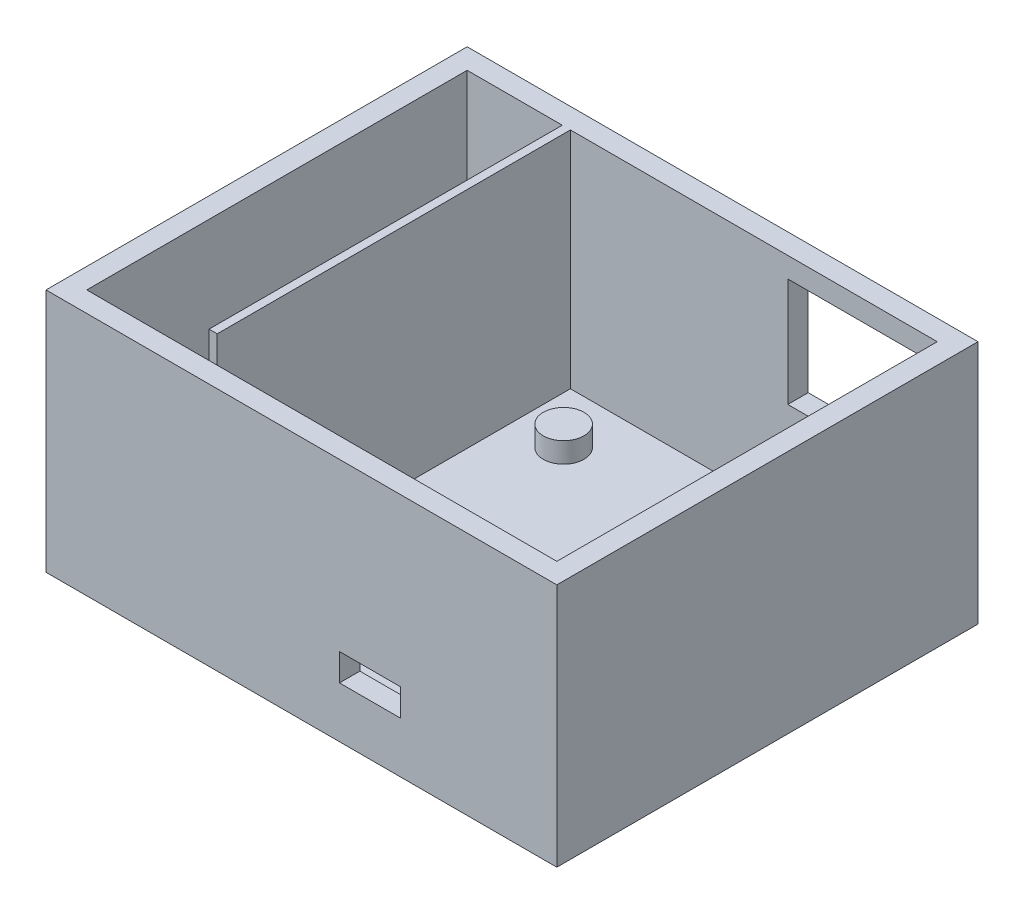
SolidWorks part; units mm, degrees
ref_plane "Front Plane" through (0, 0, 0) normal (0, 0, 1) x (1, 0, 0)
ref_plane "Top Plane" through (0, 0, 0) normal (0, 1, 0) x (1, 0, 0)
ref_plane "Right Plane" through (0, 0, 0) normal (1, 0, 0) x (0, 0, -1)
sketch "Sketch1" plane through (0, 0, 0) normal (0, 1, 0) x (1, 0, 0)
  line L0 (-55.2, 0) -> (-54, 0)
  line L1 (0, 0) -> (-54, 0)
  line L2 (0, 0) -> (0, -56)
  line L3 (0, -56) -> (-54, -56)
  line L4 (-54, 0) -> (-54, -56)
  line L5 (3, 3) -> (-72.2, 3)
  line L6 (3, 3) -> (3, -59)
  line L7 (3, -59) -> (-72.2, -59)
  line L8 (-72.2, 3) -> (-72.2, -59)
  line L9 (-69.2, 0) -> (-55.2, 0)
  line L10 (-69.2, 0) -> (-69.2, -56)
  line L11 (-69.2, -56) -> (-55.2, -56)
  line L12 (-55.2, 0) -> (-55.2, -56)
  line L13 (-55.2, -56) -> (-54, -56)
  circle A0 centre (-47, -8) radius 3
  circle A1 centre (-5, -8) radius 3
  circle A2 centre (-5, -50) radius 3
  circle A3 centre (-47, -50) radius 3
  point P21 (0, 0)
  point P22 (0, 0)
  point P23 (0, 0)
  point P24 (0, 0)
  point P25 (0, 0)
  dimension "D9" = 6
  dimension "D1" = 3
  dimension "D2" = 3
  dimension "D3" = 1.2
  dimension "D4" = 3
  dimension "D5" = 56
  dimension "D6" = 3
  dimension "D7" = 54
  dimension "D8" = 14
  dimension "D10" = 5
  dimension "D12" = 6
  dimension "D13" = 42
  dimension "D15" = 42
extrude "Boss-Extrude1" add sketch "Sketch1" along normal blind 3 contours L12 L9 L10 L11 | L12 L13 L4 L0 | A0 | A1 | A2 | A3 | L1 L4 L3 L2 A3 A2 A1 A0 | L5 L8 L7 L6 L13 L11 L10 L9 L0 L1 L2 L3 region at (-62.2, 0, 28) region at (-54.6, 0, 28) region at (-27.0389, 0, 27.9611) region at (2.0254, 0, 28) region at (-47, 0, 8) region at (-5, 0, 8) region at (-5, 0, 50) region at (-47, 0, 50)
extrude "Boss-Extrude2" add sketch "Sketch1<3>" along normal blind 3 from surface contours A3 | A2 | A1 | A0 region at (-47, 0, 8) region at (-5, 0, 8) region at (-5, 0, 50) region at (-47, 0, 50) starting at face at (-34.6, 3, 28)
sketch "Sketch1<3>" plane through (0, 0, 0) normal (0, 1, 0) x (1, 0, 0) same geometry as "Sketch1"
extrude "Boss-Extrude3" add sketch "Sketch1<4>" along normal blind 33 from surface contours L5 L8 L7 L6 L13 L11 L10 L9 L0 L1 L2 L3 | L12 L13 L4 L0 region at (-54.6, 0, 28) region at (2.0254, 0, 28) starting at face at (-47, 3, 11)
sketch "Sketch1<4>" plane through (0, 0, 0) normal (0, 1, 0) x (1, 0, 0) same geometry as "Sketch1"
sketch "Sketch2" plane through (0, 0, 59) normal (0, 0, 1) x (1, 0, 0)
  line L0 (3, 0) -> (-72.2, 0) construction
  line L1 (-29, 7.5) -> (-20, 7.5)
  line L2 (-29, 7.5) -> (-29, 11.5)
  line L3 (-29, 11.5) -> (-20, 11.5)
  line L4 (-20, 7.5) -> (-20, 11.5)
  line L5 (3, 36) -> (3, 0) construction
  dimension "D1" = 9
  dimension "D2" = 4
  dimension "D3" = 7.5
  dimension "D4" = 23
extrude "Cut-Extrude1" cut sketch "Sketch2" against normal up to next
sketch "Sketch3" plane through (-55.2, 0, 0) normal (-1, 0, 0) x (0, 0, 1)
  line L1 (56, 36) -> (52, 36)
  line L2 (56, 36) -> (56, 24)
  line L3 (56, 24) -> (52, 24)
  line L4 (52, 36) -> (52, 24)
  dimension "D1" = 12
  dimension "D2" = 4
extrude "Cut-Extrude2" cut sketch "Sketch3" against normal up to next
sketch "Sketch4" plane through (0, 0, -3) normal (0, 0, -1) x (-1, 0, 0)
  line L0 (-3, 0) -> (72.2, 0) construction
  line L1 (2, 33) -> (22, 33)
  line L2 (2, 33) -> (2, 17)
  line L3 (2, 17) -> (22, 17)
  line L4 (22, 33) -> (22, 17)
  line L5 (-3, 36) -> (-3, 0) construction
  dimension "D1" = 20
  dimension "D2" = 16
  dimension "D3" = 17
  dimension "D4" = 5
extrude "Cut-Extrude3" cut sketch "Sketch4" against normal up to next
